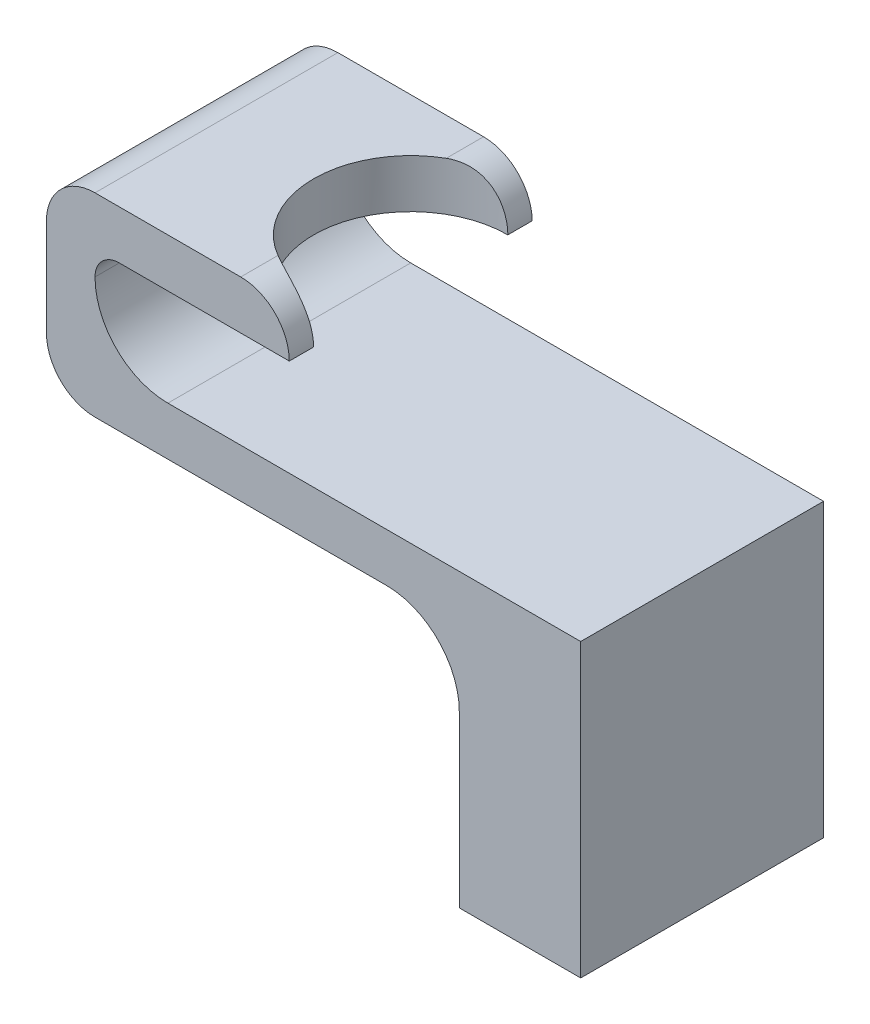
SolidWorks part; units mm, degrees
ref_plane "Plan de face" through (0, 0, 0) normal (0, 0, 1) x (1, 0, 0)
ref_plane "Plan de dessus" through (0, 0, 0) normal (0, 1, 0) x (1, 0, 0)
ref_plane "Plan de droite" through (0, 0, 0) normal (1, 0, 0) x (0, 0, -1)
sketch "Esquisse2" plane through (0, 0, 0) normal (0, 0, 1) x (1, 0, 0)
  line L0 (-35, 90) -> (-85, 90)
  line L1 (-85, 90) -> (-85, 50)
  line L2 (-85, 50) -> (0, 50)
  line L3 (0, 50) -> (0, 0)
  line L4 (0, 0) -> (25, 0)
  line L5 (25, 0) -> (25, 60)
  line L6 (25, 60) -> (-75, 60)
  line L7 (-75, 60) -> (-75, 80)
  line L8 (-75, 80) -> (-35, 80)
  line L9 (-35, 80) -> (-35, 90)
  dimension "D1" = 50
  dimension "D2" = 10
  dimension "D3" = 40
  dimension "D4" = 50
  dimension "D5" = 60
  dimension "D6" = 25
  dimension "D7" = 100
  dimension "D8" = 40
extrude "Boss.-Extru.1" add sketch "Esquisse2" along normal blind 50 contours L5 L6 L7 L8 L9 L0 L1 L2 L3 L4
sketch "Esquisse3" plane through (0, 90, 0) normal (0, 1, 0) x (1, 0, 0)
  line L0 (-35, -50) -> (-35, 0) construction
  circle A0 centre (-35, -25) radius 20
  dimension "D1" = 40
  dimension "D2" = 25
extrude "Enlèv. mat.-Extru.1" cut sketch "Esquisse3" against normal blind 10 contours A0
fillet "Congé1" radius 15 2 edges at (0, 50, 25) (-75, 60, 25)
fillet "Congé2" radius 5 1 edges at (-75, 80, 25)
fillet "Congé4" radius 10 2 edges at (-85, 50, 25) (-85, 90, 25)
fillet "Congé5" radius 10 2 edges at (-35, 90, 2.5) (-35, 90, 47.5)
